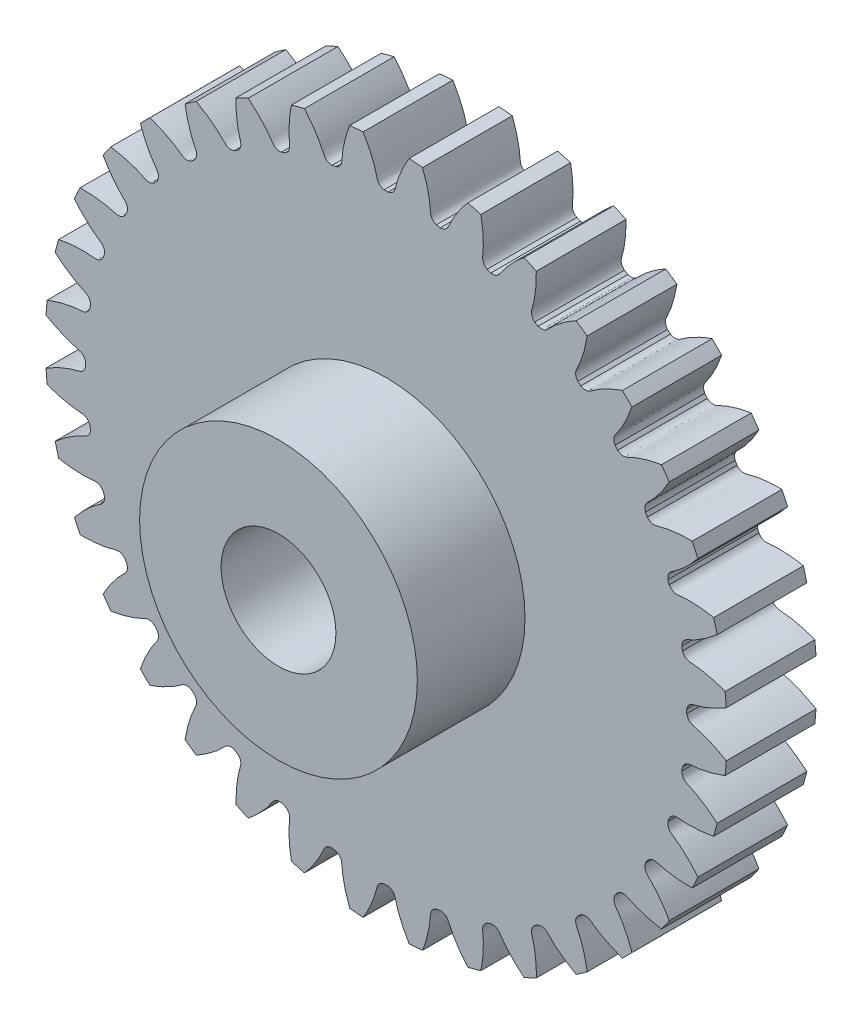
SolidWorks part; units mm, degrees
ref_plane "前视基准面" through (0, 0, 0) normal (0, 0, 1) x (1, 0, 0)
ref_plane "上视基准面" through (0, 0, 0) normal (0, 1, 0) x (1, 0, 0)
ref_plane "右视基准面" through (0, 0, 0) normal (1, 0, 0) x (0, 0, -1)
other "Configuration Table"
sketch "草图1" plane through (0, 0, 0) normal (0, 0, 1) x (1, 0, 0)
  circle A0 centre (0, 0) radius 9.5
extrude "凸台-拉伸1" add sketch "草图1" along normal blind 2.5
ref_axis "基准轴1" through (0, 0, 2.5) along (0, 0, -1)
sketch "草图2" plane through (0, 0, 0) normal (0, 0, 1) x (1, 0, 0)
  line L0 (0, 0) -> (0, 9.5) construction
  circle A0 centre (0, 0) radius 9.5 construction
  arc A1 (0.0549, 8.3748) -> (-0.0549, 8.3748) centre (0, 0) ccw
  arc A2 (1.757, 10.7884) -> (-1.757, 10.7884) centre (0, 0) ccw
  spline S0 degree 3 poles (0.0549, 8.3748) (0.235, 8.4152) (0.2505, 8.5493) (0.2882, 8.6914) (0.2997, 8.7319) (0.3131, 8.7753) (0.3284, 8.8217) (0.3457, 8.871) (0.3652, 8.9231) (0.3869, 8.9779) (0.4111, 9.0354) (0.4378, 9.0956) (0.4671, 9.1582) (0.4992, 9.2232) (0.5341, 9.2907) (0.5719, 9.3603) (0.6128, 9.4322) (0.6569, 9.5061) (0.7043, 9.582) (0.755, 9.6598) (0.8091, 9.7393) (0.8668, 9.8205) (0.9281, 9.9032) (0.9931, 9.9874) (1.0619, 10.0729) (1.1346, 10.1596) (1.2112, 10.2474) (1.2919, 10.3361) (1.3766, 10.4256) (1.4655, 10.5159) (1.5912, 10.6386) (1.6895, 10.7288) (1.757, 10.7884) knots 0 0 0 0 0.120371 0.133303 0.147364 0.162556 0.178878 0.19633 0.214913 0.234626 0.255469 0.277443 0.300547 0.324782 0.350146 0.376641 0.404267 0.433023 0.462909 0.493925 0.526072 0.559349 0.593757 0.629294 0.665963 0.703761 0.74269 0.782749 0.823939 0.866258 0.909709 1 1 1 1
  spline S1 degree 3 poles (-0.0549, 8.3748) (-0.235, 8.4152) (-0.2505, 8.5493) (-0.2882, 8.6914) (-0.2997, 8.7319) (-0.3131, 8.7753) (-0.3284, 8.8217) (-0.3457, 8.871) (-0.3652, 8.9231) (-0.3869, 8.9779) (-0.4111, 9.0354) (-0.4378, 9.0956) (-0.4671, 9.1582) (-0.4992, 9.2232) (-0.5341, 9.2907) (-0.5719, 9.3603) (-0.6128, 9.4322) (-0.6569, 9.5061) (-0.7043, 9.582) (-0.755, 9.6598) (-0.8091, 9.7393) (-0.8668, 9.8205) (-0.9281, 9.9032) (-0.9931, 9.9874) (-1.0619, 10.0729) (-1.1346, 10.1596) (-1.2112, 10.2474) (-1.2919, 10.3361) (-1.3766, 10.4256) (-1.4655, 10.5159) (-1.5912, 10.6386) (-1.6895, 10.7288) (-1.757, 10.7884) knots 0 0 0 0 0.120371 0.133303 0.147364 0.162556 0.178878 0.19633 0.214913 0.234626 0.255469 0.277443 0.300547 0.324782 0.350146 0.376641 0.404267 0.433023 0.462909 0.493925 0.526072 0.559349 0.593757 0.629294 0.665963 0.703761 0.74269 0.782749 0.823939 0.866258 0.909709 1 1 1 1
extrude "切除-拉伸1" cut sketch "草图2" along normal through all
pattern_circular "阵列(圆周)1" count 36 every 10 about axis through (0, 0, 2.5) along (0, 0, -1) of "切除-拉伸1"
sketch "草图3" plane through (0, 0, 0) normal (0, 0, 1) x (1, 0, 0)
  circle A0 centre (0, 0) radius 9 construction
  dimension "Dn" = 18
sketch "草图4" plane through (0, 0, 0) normal (0, 0, -1) x (-1, 0, 0)
  circle A0 centre (0, 0) radius 3.87
  dimension "D1" = 7.74
extrude "凸台-拉伸2" add sketch "草图4" against normal offset from surface (5.5 mm away) 3 up to face at (0, 0, 2.5) offset beyond the face yes
sketch "草图5" plane through (0, 0, 5.5) normal (0, 0, 1) x (1, 0, 0)
  circle A0 centre (0, 0) radius 1.6
  dimension "D1" = 3.2
extrude "切除-拉伸2" cut sketch "草图5" against normal up to next
